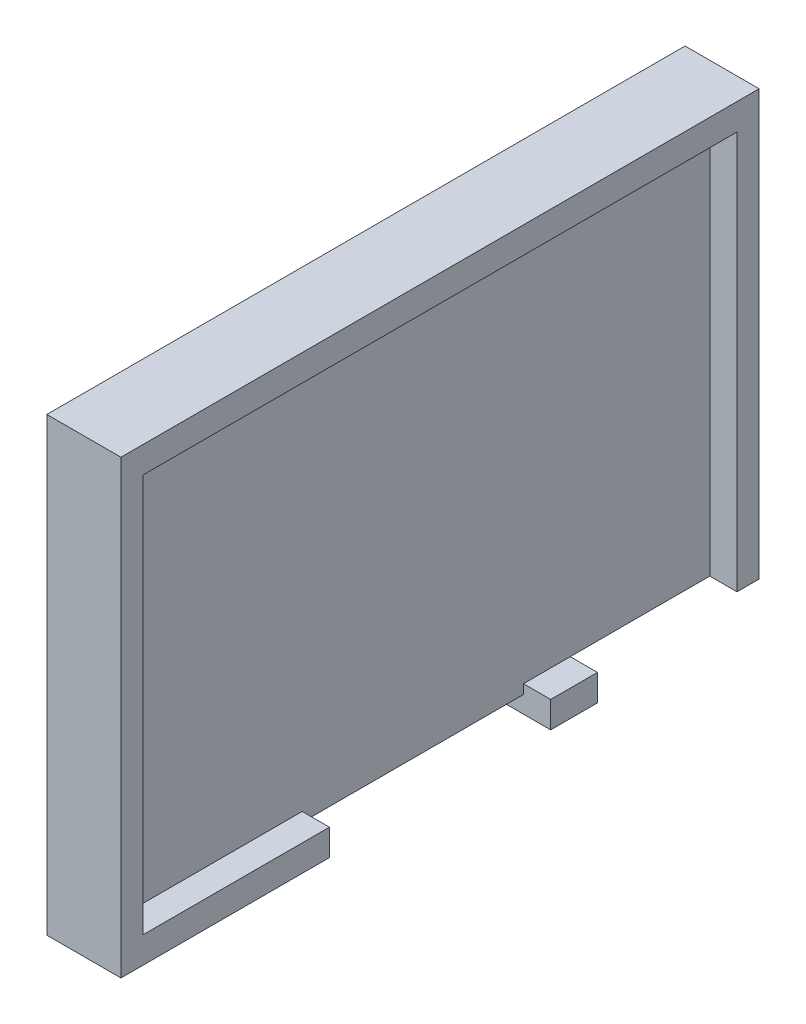
SolidWorks part; units mm, degrees
ref_plane "Front Plane" through (0, 0, 0) normal (1, 0, 0) x (0, 1, 0)
ref_plane "Top Plane" through (0, 0, 0) normal (0, 0, 1) x (0, 1, 0)
ref_plane "Right Plane" through (0, 0, 0) normal (0, 1, 0) x (-1, 0, 0)
sketch "Sketch1" plane through (0, 0, 0) normal (1, 0, 0) x (0, 1, 0)
  line L0 (42.12, 117.43) -> (42.12, 129.18) construction
  line L1 (44.62, 126.68) -> (71.12, 126.68)
  line L2 (44.62, 126.68) -> (44.62, 89.18)
  line L3 (44.62, 89.18) -> (71.12, 89.18)
  line L4 (71.12, 126.68) -> (71.12, 89.18)
  line L5 (42.12, 129.18) -> (89.12, 129.18) construction
  dimension "D1" = 26.5
  dimension "D2" = 37.5
  dimension "D3" = 2.5
  dimension "D4" = 2.5
extrude "Boss-Extrude1" add sketch "Sketch1" along normal blind 4.353 contours L2 L3 L4 L1
sketch "Sketch2" plane through (4.353, 0, 0) normal (1, 0, 0) x (0, 1, 0)
  line L0 (57.87, 126.68) -> (57.87, 89.18)
  line L1 (44.62, 126.68) -> (71.12, 126.68) construction
  line L2 (44.62, 89.18) -> (71.12, 89.18) construction
  line L3 (44.62, 107.93) -> (71.12, 107.93)
  line L4 (44.62, 126.68) -> (44.62, 89.18) construction
  line L5 (71.12, 126.68) -> (71.12, 89.18) construction
  line L7 (69.57, 90.48) -> (46.17, 90.48)
  line L8 (69.57, 90.48) -> (69.57, 125.38)
  line L9 (69.57, 125.38) -> (46.17, 125.38)
  line L10 (46.17, 90.48) -> (46.17, 125.38)
  line L11 (69.57, 90.48) -> (46.17, 125.38) construction
  line L12 (69.57, 125.38) -> (46.17, 90.48) construction
  point P12 (57.87, 107.93)
  dimension "D1" = 23.4
  dimension "D2" = 34.9
extrude "Cut-Extrude1" cut sketch "Sketch2" against normal blind 1.6 contours L7 L10 L9 L8
sketch "Sketch3" plane through (4.353, 0, 0) normal (1, 0, 0) x (0, 1, 0)
  line L0 (44.62, 107.93) -> (46.17, 107.93)
  line L1 (44.62, 126.68) -> (44.62, 89.18) construction
  line L2 (46.17, 90.48) -> (46.17, 125.38) construction
  line L3 (46.17, 125.38) -> (46.17, 126.68)
  line L4 (44.62, 126.68) -> (71.12, 126.68) construction
  line L5 (45.395, 107.93) -> (45.395, 126.68)
  line L7 (46.17, 101.43) -> (44.62, 101.43)
  line L8 (46.17, 101.43) -> (46.17, 114.43)
  line L9 (46.17, 114.43) -> (44.62, 114.43)
  line L10 (44.62, 101.43) -> (44.62, 114.43)
  line L11 (46.17, 101.43) -> (44.62, 114.43) construction
  line L12 (46.17, 114.43) -> (44.62, 101.43) construction
  dimension "D1" = 13
extrude "Cut-Extrude2" cut sketch "Sketch3" against normal blind 1.6 contours L7 L10 L9 L8
sketch "Sketch4" plane through (0, 44.62, 0) normal (0, -1, 0) x (1, 0, 0)
  line L0 (0, 126.68) -> (0, 89.18) construction
  line L1 (2.753, 101.43) -> (0, 101.43)
  line L2 (2.753, 101.43) -> (2.753, 114.43)
  line L3 (2.753, 114.43) -> (0, 114.43)
  line L4 (0, 101.43) -> (0, 114.43)
extrude "Cut-Extrude3" cut sketch "Sketch4" against normal blind 1
sketch "Sketch5" plane through (4.353, 0, 0) normal (1, 0, 0) x (0, 1, 0)
  line L0 (46.17, 90.48) -> (46.17, 101.43) construction
  line L1 (44.62, 89.18) -> (46.17, 89.18)
  line L2 (44.62, 89.18) -> (44.62, 98.68)
  line L3 (44.62, 98.68) -> (46.17, 98.68)
  line L4 (46.17, 89.18) -> (46.17, 98.68)
  dimension "D1" = 9.5
extrude "Cut-Extrude5" cut sketch "Sketch5" against normal blind 1.6 contours L2 L1 L4 L3
sketch "Sketch6" plane through (0, 0, 89.18) normal (0, 0, -1) x (1, 0, 0)
  line L0 (4.353, -46.17) -> (1.953, -46.17)
  line L1 (1.953, -46.17) -> (1.953, -49.12)
  line L2 (1.953, -49.12) -> (0, -49.12)
  line L3 (0, -44.62) -> (0, -71.12) construction
  line L4 (0, -49.12) -> (0, -44.62)
  line L5 (0, -44.62) -> (2.753, -44.62)
  line L6 (2.753, -44.62) -> (2.753, -46.17)
  line M1 (2.753, -46.17) -> (2.753, -44.62)
  line M2 (2.753, -44.62) -> (0, -44.62)
  line M3 (0, -44.62) -> (0, -71.12)
  dimension "D1" = 2.4
  dimension "D2" = 2.95
extrude "Cut-Extrude6" cut sketch "Sketch6" against normal blind 9.5 contours L2 L1 L0 M1 M2 M3 region at (1.1467, 46.6876, 89.18)
sketch "Sketch7" plane through (0, 0, 0) normal (-1, 0, 0) x (0, -1, 0)
  line L0 (-49.12, 98.68) -> (-49.12, 89.18) construction
  line L1 (-66.8403, 98.7845) -> (-56.9188, 98.7845)
  line L2 (-66.8403, 98.7845) -> (-66.8403, 116.2777)
  line L3 (-66.8403, 116.2777) -> (-56.9188, 116.2777)
  line L4 (-56.9188, 98.7845) -> (-56.9188, 116.2777)
  line L5 (-57.3291, 90.6534) -> (-49.12, 90.6534)
  line L6 (-57.3291, 90.6534) -> (-57.3291, 95.8379)
  line L7 (-57.3291, 95.8379) -> (-49.12, 95.8379)
  line L8 (-49.12, 90.6534) -> (-49.12, 95.8379)
  line L10 (-54.8301, 122.5066) -> (-50.2424, 122.5066)
  line L11 (-54.8301, 122.5066) -> (-54.8301, 95.8379)
  line L12 (-54.8301, 95.8379) -> (-50.2424, 95.8379)
  line L13 (-50.2424, 122.5066) -> (-50.2424, 95.8379)
  line M22 (-49.12, 89.18) -> (-49.12, 98.68)
extrude "Cut-Extrude7" cut sketch "Sketch7" against normal blind 2 contours L13 L10 L11 L7 | L7 L6 L5 M22 | L1 L4 L3 L2 region at (0, 61.8796, 107.5311) region at (0, 53.2246, 93.2457) region at (0, 52.5362, 109.1723)
sketch "Sketch8" plane through (0, 0, 0) normal (-1, 0, 0) x (0, -1, 0)
  line L0 (-68.22, 121.18) -> (-68.195, 94.68)
  line L1 (-67.32, 121.18) -> (-69.12, 121.18) construction
  line L2 (-69.095, 94.68) -> (-67.295, 94.68) construction
  line L3 (-68.2075, 107.93) -> (-42.7917, 107.93)
  line L4 (-67.32, 123.18) -> (-47.92, 123.18)
  line L5 (-67.32, 125.18) -> (-67.32, 121.18) construction
  line L6 (-47.92, 121.18) -> (-47.92, 125.18) construction
  line L7 (-57.62, 123.18) -> (-57.62, 84.9383)
ref_plane "Plane2" through (0, 57.62, 0) normal (0, -1, 0) x (1, 0, 0)
ref_plane "Plane3" through (0, 0, 107.93) normal (0, 0, 1) x (0, -1, 0)
sketch "Sketch10" plane through (0, 0, 0) normal (-1, 0, 0) x (0, -1, 0)
  line L0 (-67.52, 124.98) -> (-67.52, 121.38)
  line L1 (-67.32, 125.18) -> (-69.12, 125.18)
  line L2 (-67.32, 125.18) -> (-67.32, 121.18)
  line L3 (-67.32, 121.18) -> (-69.12, 121.18)
  line L4 (-69.12, 125.18) -> (-69.12, 121.18)
  line L5 (-67.52, 121.38) -> (-68.92, 121.38)
  line L6 (-68.92, 124.98) -> (-68.92, 121.38)
  line L7 (-67.52, 124.98) -> (-68.92, 124.98)
  point P10 (0, 0)
  point P11 (0, 0)
  dimension "D1" = 0.2
extrude "Boss-Extrude3" add sketch "Sketch10" along normal blind 1.6 contours L6 L5 L0 L7
mirror "Mirror1" about plane through (0, 57.62, 0) normal (0, -1, 0) of "Boss-Extrude3"
mirror "Mirror2" about plane through (0, 0, 107.93) normal (0, 0, 1) of "Boss-Extrude3"
